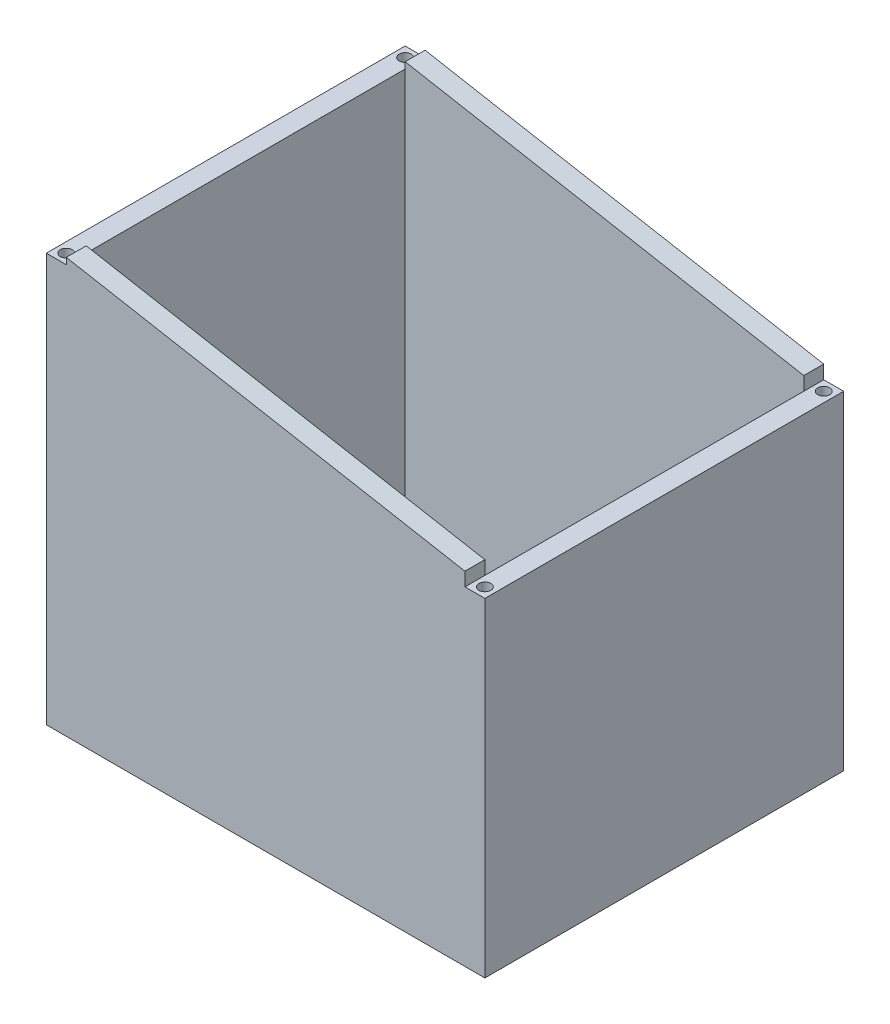
SolidWorks part; units mm, degrees
ref_plane "Front Plane" through (0, 0, 0) normal (0, 0, 1) x (1, 0, 0)
ref_plane "Top Plane" through (0, 0, 0) normal (0, 1, 0) x (1, 0, 0)
ref_plane "Right Plane" through (0, 0, 0) normal (1, 0, 0) x (0, 0, -1)
sketch "Sketch1" plane through (0, 0, 0) normal (0, 1, 0) x (1, 0, 0)
  line L0 (-55, 45) -> (-55, -45)
  line L1 (-55, -45) -> (55, -45)
  line L2 (-55, -45) -> (-55, 45)
  line L3 (-55, 45) -> (55, 45)
  line L4 (55, -45) -> (55, 45)
  line L5 (-55, -45) -> (55, 45) construction
  line L6 (-55, 45) -> (55, -45) construction
  line L7 (-55, 45) -> (-50, 45)
  line L8 (-55, -45) -> (-50, -45)
  line L9 (-50, 45) -> (-50, -45)
  line L10 (55, 45) -> (55, -45)
  line L11 (55, 45) -> (50, 45)
  line L12 (55, -45) -> (50, -45)
  line L13 (50, 45) -> (50, -45)
  line L14 (-50, -45) -> (50, -45)
  line L15 (-50, -45) -> (-50, -40)
  line L16 (50, -45) -> (50, -40)
  line L17 (-50, -40) -> (50, -40)
  line L18 (-50, 45) -> (50, 45)
  line L19 (-50, 45) -> (-50, 40)
  line L20 (50, 45) -> (50, 40)
  line L21 (-50, 40) -> (50, 40)
  point P0 (0, 0)
  dimension "D1" = 110
  dimension "D2" = 90
  dimension "D3" = 5
  dimension "D4" = 5
  dimension "D5" = 5
  dimension "D6" = 5
extrude "Boss-Extrude3" add sketch "Sketch1" along normal blind 80 and the other way blind 24.9608 contours L9 L21 L13 L3 | L9 L3 L0 L1 | L3 L13 L1 L4 | L17 L9 L1 L13 region at (-52.5, 0, 0) region at (0, 0, -42.5) region at (0, 0, 42.5) region at (52.5, 0, 0)
sketch "Sketch2" plane through (0, 80, 0) normal (0, 1, 0) x (1, 0, 0)
  line L0 (-50, 40) -> (-55, 45) construction
  circle A0 centre (-52.5, 42.5) radius 1.5
extrude "Cut-Extrude1" cut sketch "Sketch2" against normal blind 80
sketch "Sketch3" plane through (0, 80, 0) normal (0, 1, 0) x (1, 0, 0)
  line L0 (55, 45) -> (50, 40) construction
  circle A0 centre (52.5, 42.5) radius 1.5
extrude "Cut-Extrude2" cut sketch "Sketch3" against normal blind 80
sketch "Sketch4" plane through (0, 80, 0) normal (0, 1, 0) x (1, 0, 0)
  line L0 (-55, -45) -> (-50, -40) construction
  circle A0 centre (-52.5, -42.5) radius 1.5
extrude "Cut-Extrude3" cut sketch "Sketch4" against normal blind 80
sketch "Sketch5" plane through (0, 80, 0) normal (0, 1, 0) x (1, 0, 0)
  line L0 (50, -40) -> (55, -45) construction
  line L1 (-50, -40) -> (50, -40) construction
  line L2 (-55, -45) -> (55, -45) construction
  circle A0 centre (52.5, -42.5) radius 1.5
extrude "Cut-Extrude4" cut sketch "Sketch5" against normal blind 80
sketch "Sketch6" plane through (0, 0, 45) normal (0, 0, 1) x (1, 0, 0)
  line L0 (-55, 80) -> (55, 80)
  line L1 (55, 80) -> (55, 60)
  line L2 (55, 80) -> (55, -24.9608) construction
  line L3 (55, 60) -> (-55, 80)
  dimension "D1" = 20
extrude "Cut-Extrude5" cut sketch "Sketch6" against normal blind 90
sketch "Sketch7" plane through (55, 0, 0) normal (1, 0, 0) x (0, 0, -1)
  line L0 (45, 60) -> (45, -24.9608) construction
  line L1 (-45, 60) -> (45, 60)
  line L2 (-45, 60) -> (-45, 57.5)
  line L3 (-45, 57.5) -> (45, 57.5)
  line L4 (45, 60) -> (45, 57.5)
  dimension "D1" = 2.5
extrude "Cut-Extrude7" cut sketch "Sketch7" against normal blind 5
sketch "Sketch8" plane through (0, 0, 45) normal (0, 0, 1) x (1, 0, 0)
  line L0 (50, 60) -> (55, 60)
  line L1 (55, 60) -> (50, 60.9091)
  line L2 (-55, 80) -> (55, 60) construction
  line L3 (50, 60.9091) -> (50, 60)
extrude "Cut-Extrude8" cut sketch "Sketch8" against normal blind 90
sketch "Sketch9" plane through (0, 0, 45) normal (0, 0, 1) x (1, 0, 0)
  line L0 (-55, 80) -> (-55, 77.5)
  line L1 (-55, 80) -> (-55, -24.9608) construction
  line L2 (-55, 77.5) -> (-50, 77.5)
  line L3 (-50, 77.5) -> (-50, 79.0909)
  line L4 (-55, 80) -> (50, 60.9091) construction
  line L5 (-50, 79.0909) -> (-55, 80)
  dimension "D1" = 2.5
  dimension "D2" = 5
extrude "Cut-Extrude11" cut sketch "Sketch9" against normal blind 90
extrude "Cut-Extrude17" cut sketch "Sketch4<3>" against normal blind 105
sketch "Sketch4<3>" plane through (0, 80, 0) normal (0, 1, 0) x (1, 0, 0) same geometry as "Sketch4"
extrude "Cut-Extrude18" cut sketch "Sketch5<3>" against normal blind 105
sketch "Sketch5<3>" plane through (0, 80, 0) normal (0, 1, 0) x (1, 0, 0) same geometry as "Sketch5"
extrude "Cut-Extrude19" cut sketch "Sketch3<3>" against normal blind 105
sketch "Sketch3<3>" plane through (0, 80, 0) normal (0, 1, 0) x (1, 0, 0) same geometry as "Sketch3"
extrude "Cut-Extrude20" cut sketch "Sketch2<3>" against normal blind 105
sketch "Sketch2<3>" plane through (0, 80, 0) normal (0, 1, 0) x (1, 0, 0) same geometry as "Sketch2"
sketch "Sketch20" plane through (-55, 0, 0) normal (-1, 0, 0) x (0, 0, 1)
  line L1 (-45, -24.9608) -> (45, -24.9608) construction
  line L7 (-29, -11.9608) -> (29, -11.9608)
  line L8 (-29, -11.9608) -> (-29, -24.9608)
  line L9 (-29, -24.9608) -> (29, -24.9608)
  line L10 (29, -11.9608) -> (29, -24.9608)
extrude "Cut-Extrude21" cut sketch "Sketch20" against normal blind 5
